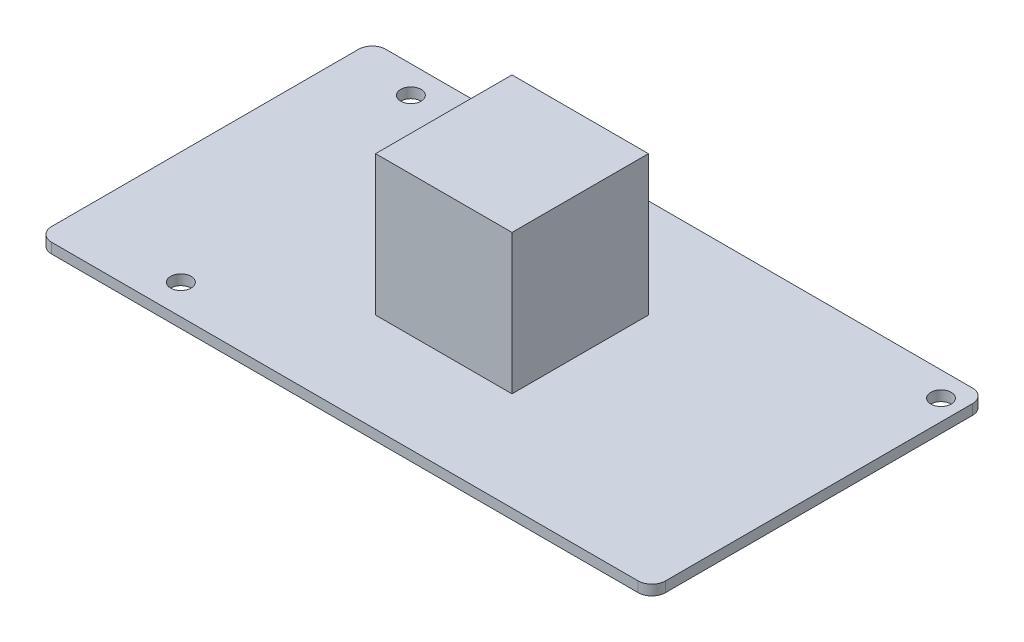
SolidWorks part; units mm, degrees
ref_plane "Front Plane" through (0, 0, 0) normal (0, 0, 1) x (1, 0, 0)
ref_plane "Top Plane" through (0, 0, 0) normal (0, 1, 0) x (1, 0, 0)
ref_plane "Right Plane" through (0, 0, 0) normal (1, 0, 0) x (0, 0, -1)
sketch "Sketch1" plane through (0, 0, 0) normal (0, 1, 0) x (1, 0, 0)
  line L1 (-45, -24.5) -> (45, -24.5)
  line L2 (-45, -24.5) -> (-45, 24.5)
  line L3 (-45, 24.5) -> (45, 24.5)
  line L4 (45, -24.5) -> (45, 24.5)
  line L5 (-45, -24.5) -> (45, 24.5) construction
  line L6 (-45, 24.5) -> (45, -24.5) construction
  point P0 (0, 0)
  dimension "D1" = 90
  dimension "D2" = 49
extrude "Boss-Extrude1" add sketch "Sketch1" along normal blind 1.5
fillet "Fillet1" radius 2 4 edges at (-45, 0.75, -24.5) (45, 0.75, -24.5) (45, 0.75, 24.5) (-45, 0.75, 24.5)
hole_wizard "Ø1.0mm Dowel Hole1" positions "Sketch2" profile "Sketch3" hole size "Ø1.0" standard "ANSI Metric" end condition through all
sketch "Sketch2" plane through (0, 1.5, 0) normal (0, 1, 0) x (1, 0, 0)
  line L0 (-45, 22.5) -> (-45, -22.5) construction
  line L1 (43, 24.5) -> (-43, 24.5) construction
  line L2 (45, -22.5) -> (45, 22.5) construction
  line L3 (-43, -24.5) -> (43, -24.5) construction
  point P0 (-35.325, 20.5)
  point P2 (42, 20.9)
  point P4 (-28.45, -20.1)
  dimension "D1" = 9.675
  dimension "D2" = 4
  dimension "D3" = 3.6
  dimension "D4" = 3
  dimension "D5" = 16.55
  dimension "D6" = 4.4
  dimension "D7" = 77.325
sketch "Sketch3" plane through (-35.325, 1.5, -20.5) normal (1, 0, 0) x (0, 0, 1)
  line L0 (0, 0) -> (0, 1.5)
  line L1 (0, 1.5) -> (1.5, 1.5)
  line L2 (1.5, 1.5) -> (1.5, 0)
  line L5 (1.5, 0) -> (0, 0)
  line L11 (0, -6.35) -> (0, 107.95) construction
  dimension "Thru Hole Dia." = 3
  dimension "Thru Hole Depth" = 1.5
sketch "Sketch4" plane through (0, 0, 0) normal (0, -1, 0) x (1, 0, 0)
  line L1 (10, -10) -> (-10, -10)
  line L2 (10, -10) -> (10, 10)
  line L3 (10, 10) -> (-10, 10)
  line L4 (-10, -10) -> (-10, 10)
  line L5 (10, -10) -> (-10, 10) construction
  line L6 (10, 10) -> (-10, -10) construction
  point P0 (0, 0)
  dimension "D1" = 20
  dimension "D2" = 20
extrude "Boss-Extrude2" add sketch "Sketch4" against normal blind 22
